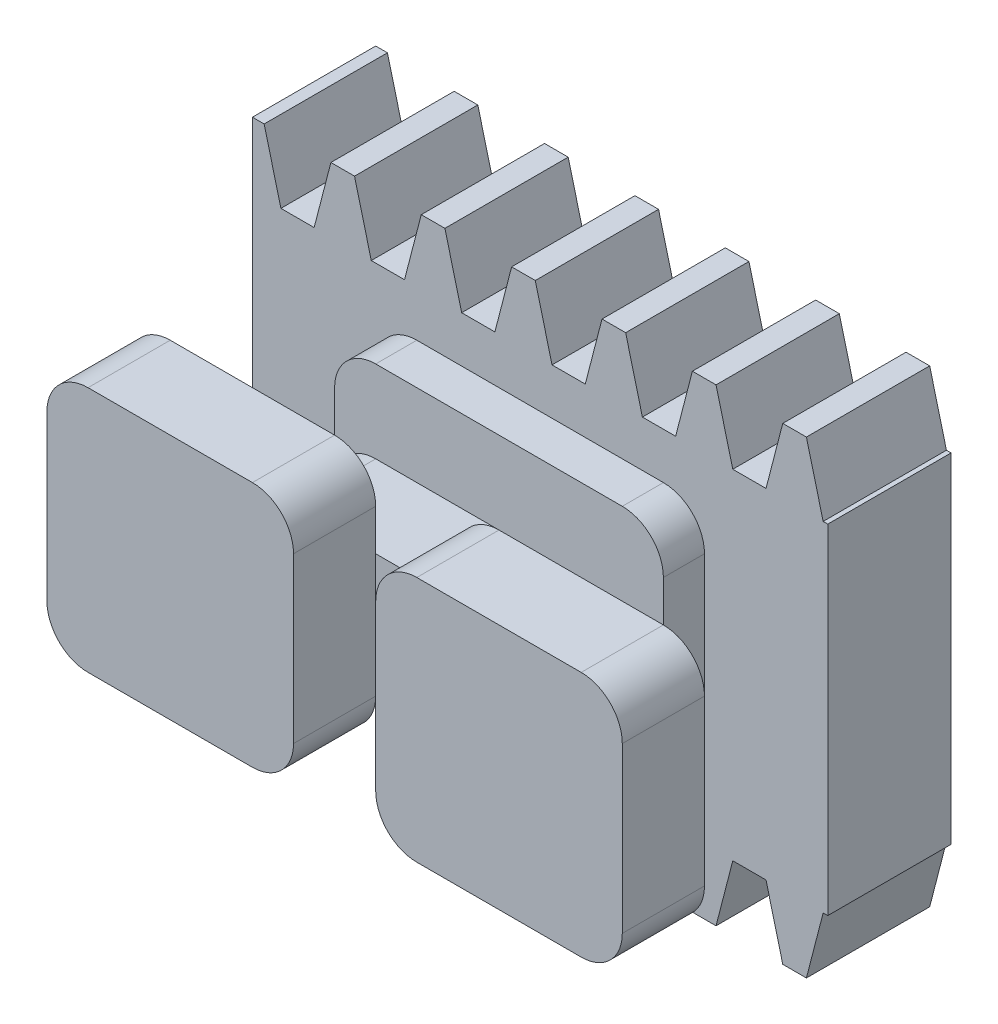
SolidWorks part; units mm, degrees
extrude "Blank" add sketch "BlankSke" against normal blind 3
sketch "BlankSke" plane through (0, 0, 0) normal (0, 0, 1) x (1, 0, 0)
  line L1 (0, 0) -> (25, 0)
  line L2 (0, 0) -> (0, 5.7)
  line L3 (0, 5.7) -> (25, 5.7)
  line L4 (25, 0) -> (25, 5.7)
  dimension "Length" = 25
ref_plane "Plane1" through (0, 0, 0) normal (0, 0, 1) x (1, 0, 0)
ref_plane "Plane2" through (0, 0, 0) normal (0, 1, 0) x (1, 0, 0)
ref_plane "Plane3" through (0, 0, 0) normal (1, 0, 0) x (0, 0, -1)
other "Configuration Table"
sketch "HoldingSke" plane through (0, 0, 0) normal (0, 1, 0) x (1, 0, 0)
  line L0 (0, 0) -> (0.1988, 1.4147)
  line L1 (-15, 0) -> (100, 0) construction
  line L2 (0, 0) -> (-2.1039, 2.3779)
  line L3 (0, 0) -> (-11.863, 4.5341)
  line L4 (0, 0) -> (8.4147, 1.9427)
  line L5 (0, 0) -> (-23.7986, -8.8762)
  line L6 (0, 0) -> (-10.5278, -7.1032)
  line L9 (-67.7845, 28.3722) -> (-43.5808, 34.6317)
  line L10 (-76.2, 3.0779) -> (-71.2, 3.0779)
  line L11 (0, 0) -> (-3, 0)
  line L12 (-76.2, 101.6) -> (-76.173, 101.6)
  line L13 (24.9733, 27.94) -> (52.9518, 28.4284)
  line L14 (24.9733, 27.94) -> (24.9743, 27.94)
  line L15 (24.9733, 27.94) -> (100.4006, 29.5858)
  circle A0 centre (0, 0) radius 19.05
  circle A1 centre (0, 0) radius 2.5
  circle A2 centre (0, 0) radius 12.7
  dimension "Num_teeth" = 13
  dimension "Width" = 3
  dimension "Length" = 25
  dimension "Pitch_height" = 5
sketch "TooCutSkeIll" plane through (0, 0, 0) normal (0, 0, 1) x (1, 0, 0)
  line L0 (-0.8064, 5.679) -> (-0.4386, 4.2569)
  line L1 (-0.2682, 4.125) -> (0.2682, 4.125)
  line L2 (0.4386, 4.2569) -> (0.8064, 5.679)
  line L3 (25, 5.7) -> (0, 5.7) construction
  line L4 (0, 0) -> (0, 64.897) construction
  line L5 (-13.208, 5) -> (12.954, 5) construction
  line L6 (0, 0) -> (25, 0) construction
  line L7 (0.6308, 5) -> (0.6308, 48.7463) construction
  line L8 (-0.6308, 5) -> (-0.6308, 48.7463) construction
  line L9 (0.8335, 5.7) -> (0.8335, 5.7254)
  line L10 (-0.8335, 5.7) -> (-0.8335, 5.7254)
  line L11 (-0.8335, 5.7254) -> (0.8335, 5.7254)
  arc A0 (0.2682, 4.125) -> (0.4386, 4.2569) centre (0.2682, 4.301) ccw
  arc A1 (-0.4386, 4.2569) -> (-0.2682, 4.125) centre (-0.2682, 4.301) ccw
  arc A2 (0.8335, 5.7) -> (0.8064, 5.679) centre (0.8335, 5.672) ccw
  arc A3 (-0.8064, 5.679) -> (-0.8335, 5.7) centre (-0.8335, 5.672) ccw
  dimension "Addendum_plus" = 0.7254
  dimension "Pitch_height" = 5
  dimension "Pressure_angle" = 14.5
  dimension "Gap_width" = 1.2616
  dimension "Dedendum" = 0.875
extrude "ToothCutIll" [suppressed] cut sketch "TooCutSkeIll" against normal through all
sketch "TooCutSkeSim" plane through (0, 0, 0) normal (0, 0, 1) x (1, 0, 0)
  line L0 (0.4045, 4.125) -> (-0.4045, 4.125)
  line L1 (0.8184, 5.7254) -> (0.4045, 4.125)
  line L2 (0, 17.4625) -> (0, 53.467) construction
  line L3 (0.8184, 5.7254) -> (-0.8184, 5.7254)
  line L6 (-0.8184, 5.7254) -> (-0.4045, 4.125)
  line L9 (-0.6308, 5) -> (0.6308, 5) construction
  line L10 (0, 0) -> (25, 0) construction
  line L11 (0.6308, 5) -> (0.6308, 53.467) construction
  line L12 (-0.6308, 5) -> (-0.6308, 53.467) construction
  dimension "Addendum_plus" = 0.7254
  dimension "Pitch_height" = 5
  dimension "Pressure_angle" = 14.5
  dimension "Gap_width" = 1.2616
  dimension "Dedendum" = 0.875
extrude "ToothCutSim" cut sketch "TooCutSkeSim" against normal through all
pattern_linear "TeethCuts" count 13 spacing 2.1991 along (1, 0, 0) of "ToothCutIll", "ToothCutSim"
mirror "镜向1" [suppressed]
mirror "镜向2" about plane through (0, 0, -3) normal (0, -1, 0) of "Blank", "ToothCutSim", "TeethCuts"
sketch "草图1" plane through (0, 0, 0) normal (-1, 0, 0) x (0, 0, 1)
  line L1 (0, 4.125) -> (0, -4.125) construction
  line L4 (-3, 0) -> (0, 0) construction
  line L5 (-3, 4.125) -> (-3, -4.125) construction
  line L7 (0, -3) -> (0, 3)
  line L8 (0, 3) -> (-2, 3.5)
  line L9 (-2, 3.5) -> (-2, -3.5)
  line L10 (0, -3) -> (-2, -3.5)
  point P11 (-2.5, 0)
  point P12 (-2, 0)
  dimension "D1" = 3
  dimension "D2" = 3.5
  dimension "D3" = 2
sketch "草图2" plane through (0, 0, -3) normal (0, 0, -1) x (-1, 0, 0)
  line L0 (0, 0) -> (-25, 0) construction
  line L1 (0, 4.125) -> (0, -4.125) construction
  line L2 (-25, -5.692) -> (-25, 5.692) construction
  circle A0 centre (-12.5, 0) radius 1.5
  dimension "D1" = 3
extrude "凸台-拉伸1" add sketch "草图2" along normal blind 2.5
sketch "草图3" plane through (0, 0, -5.5) normal (0, 0, -1) x (-1, 0, 0)
  circle A0 centre (-12.5, 0) radius 0.5
  dimension "D1" = 1
extrude "切除-拉伸3" cut sketch "草图3" against normal through all
sketch "草图4" plane through (0, 0, -3) normal (0, 0, -1) x (-1, 0, 0)
  line L0 (-12.5, 0) -> (-21.8848, 0) construction
  line L1 (-12.5, 0) -> (-2.5, 0) construction
  line L2 (-21.8848, 2.1496) -> (-21.8848, -2.1496)
  line L3 (-22.3956, 4.125) -> (-22.803, 5.7) construction
  line L4 (-2.5, 4.125) -> (-2.5, -4.125)
  line L6 (-1.7946, -4.125) -> (-2.6036, -4.125) construction
  line L7 (-22.3956, -4.125) -> (-22.803, -5.7) construction
  line L9 (-1.7946, 4.125) -> (-2.6036, 4.125) construction
  line L10 (-21.8848, 2.1496) -> (-21.8848, 5.9598)
  line L11 (-21.8848, 5.9598) -> (-25.6774, 5.9598)
  line L12 (-25.6774, 5.9598) -> (-25.6774, -6.5792)
  line L13 (-25.6774, -6.5792) -> (-21.8848, -6.5792)
  line L14 (-21.8848, -6.5792) -> (-21.8848, -2.1496)
  line L15 (-2.5, 4.125) -> (-2.5, 6.4022)
  line L16 (-2.5, 6.4022) -> (0, 6.4022)
  line L17 (0, 6.4022) -> (0, -6.0736)
  line L18 (0, -6.0736) -> (-2.5, -6.0736)
  line L19 (-2.5, -6.0736) -> (-2.5, -4.125)
  dimension "D2" = 10
extrude "切除-拉伸4" cut sketch "草图4" against normal blind 10
sketch "草图5" plane through (0, 0, 0) normal (0, 0, 1) x (1, 0, 0)
  line L0 (2.5, 2) -> (21.8848, 2)
  line L1 (2.5, 4.125) -> (2.5, -4.125) construction
  line L2 (21.8848, -4.125) -> (21.8848, 4.125) construction
  line L3 (21.8848, 2) -> (21.8848, -2)
  line L4 (21.8848, -2) -> (2.5, -2)
  line L5 (2.5, -2) -> (2.5, 2)
  point P8 (2.5, 0)
  point P9 (21.8848, 0)
  dimension "D1" = 4
sketch "草图6" plane through (0, 0, 0) normal (0, 0, 1) x (1, 0, 0)
  line L0 (1.1742, 0) -> (24.2349, 0) construction
  line L1 (8.5, 1) -> (8.5, -1)
  line L2 (8.5, -1) -> (16.5, -1)
  line L3 (16.5, -1) -> (16.5, 1)
  line L4 (16.5, 1) -> (8.5, 1)
  point P2 (16.5, 0)
  point P4 (12.5, 0)
  point P5 (8.5, 0)
  dimension "D1" = 2
  dimension "D2" = 8
  dimension "D3" = 4
extrude "凸台-拉伸3" add sketch "草图6" along normal blind 3
sketch "草图7" plane through (0, 0, 3) normal (0, 0, 1) x (1, 0, 0)
  line L0 (5.5, 3) -> (11.5, 3)
  line L1 (19.5, 3) -> (19.5, -3)
  line L2 (19.5, -3) -> (13.5, -3)
  line L3 (5.5, -3) -> (5.5, 3)
  line L5 (16.5, 1) -> (8.5, 1) construction
  line L6 (8.5, -1) -> (16.5, -1) construction
  line L7 (8.5, 1) -> (8.5, -1) construction
  line L8 (16.5, -1) -> (16.5, 1) construction
  line L9 (11.5, 3) -> (11.5, -3)
  line L10 (13.5, 3) -> (13.5, -3)
  line L11 (13.5, 3) -> (19.5, 3)
  line L12 (11.5, -3) -> (5.5, -3)
  dimension "D1" = 2
  dimension "D2" = 2
  dimension "D3" = 3
  dimension "D4" = 3
  dimension "D5" = 6
  dimension "D6" = 6
extrude "凸台-拉伸4" add sketch "草图7" along normal blind 2
fillet "圆角1" radius 1 4 edges at (16.5, -1, 1.5) (8.5, -1, 1.5) (16.5, 1, 1.5) (8.5, 1, 1.5)
fillet "圆角2" radius 1 8 edges at (5.5, -3, 4) (5.5, 3, 4) (11.5, 3, 4) (11.5, -3, 4) (13.5, -3, 4) (13.5, 3, 4) (19.5, 3, 4) (19.5, -3, 4)
sketch "草图8" plane through (0, 0, 0) normal (0, 0, 1) x (1, 0, 0)
  line L15 (8.5, 3) -> (8.5, -3)
  line L16 (10.5, 3) -> (6.5, 3) construction
  line L17 (6.5, -3) -> (10.5, -3) construction
  line L18 (8.5, -3) -> (16.5, -3)
  line L19 (14.5, -3) -> (18.5, -3) construction
  line L20 (16.5, -3) -> (16.5, 3)
  line L21 (16.5, 3) -> (8.5, 3)
  line L22 (11.5, -2) -> (11.5, 2) construction
  dimension "D1" = 3
  dimension "D2" = 8
extrude "凸台-拉伸5" add sketch "草图8" along normal blind 1
fillet "圆角5" radius 1 4 edges at (16.5, -3, 0.5) (8.5, -3, 0.5) (8.5, 3, 0.5) (16.5, 3, 0.5)
sketch "草图9" plane through (0, 0, 0) normal (0, 0, 1) x (1, 0, 0)
  line L0 (5.5, 0) -> (5.5, -6.2232)
  line L1 (5.5, 2) -> (5.5, -2) construction
  line L2 (5.5, -6.2232) -> (2.2382, -6.2232)
  line L3 (2.2382, -6.2232) -> (2.2382, 6.2496)
  line L4 (2.2382, 6.2496) -> (5.5, 6.2496)
  line L5 (5.5, 6.2496) -> (5.5, 0)
  line L6 (19.5, 0) -> (19.5, -6.2232)
  line L7 (19.5, -2) -> (19.5, 2) construction
  line L8 (19.5, -6.2232) -> (22.4063, -6.2232)
  line L9 (22.4063, -6.2232) -> (22.4063, 6.2496)
  line L10 (22.4063, 6.2496) -> (19.5, 6.2496)
  line L11 (19.5, 6.2496) -> (19.5, 0)
extrude "切除-拉伸5" cut sketch "草图9" against normal through all
equation "' \"Module@HoldingSke\" = 6.35"
equation "' \"Num_teeth@HoldingSke\" = 12"
equation "' \"Ap@HoldingSke\" =  20"
equation "' \"Ap@HoldingSke\" = 20"
equation "' \"Width@HoldingSke\" = 0.25 * 25.4"
equation "' \"Show_teeth@HoldingSke\" = 500"
equation "' \"Backlash@HoldingSke\" = 0.009 * 25.4"
equation "' \"Addendum_fac@HoldingSke\" = 1.0"
equation "' \"Dedendum_fac@HoldingSke\" = 1.25"
equation "' \"Dedendum_add@HoldingSke\" = 0.00005 * 25.4"
equation "' \"Clearance_fac@HoldingSke\" = 0.25"
equation "' \"Pitch_height@HoldingSke\" = 1 * 25.4"
equation "' \"Length@HoldingSke\" = 4.71 * 25.4"
equation "\"Pitch@HoldingSke\" = 1 / \"Module@HoldingSke\""
equation "\"MPH@HoldingSke\" = \"Dedendum_fac@HoldingSke\" / \"Pitch@HoldingSke\" + 2 * \"Dedendum_add@HoldingSke\" + 0.002 * 25.4"
equation "\"MPH@HoldingSke\" = ((sgn( \"MPH@HoldingSke\" - \"Pitch_height@HoldingSke\")+1)*( \"MPH@HoldingSke\" - \"Pitch_height@HoldingSke\"))/2 + \"Pitch_height@HoldingSke\""
equation "\"Blank_height@BlankSke\" = \"Pitch_height@HoldingSke\" + \"Addendum_fac@HoldingSke\"  / \"Pitch@HoldingSke\" "
equation "\"Length@BlankSke\" =  \"Length@HoldingSke\""
equation "\"Face_width@Blank\" = \"Width@HoldingSke\""
equation "\"Pressure_angle@TooCutSkeIll\" = \"Ap@HoldingSke\""
equation "\"Addendum_plus@TooCutSkeIll\" =  \"Addendum_fac@HoldingSke\"  / \"Pitch@HoldingSke\" + 0.001 *25.4"
equation "\"Dedendum@TooCutSkeIll\" = \"Dedendum_fac@HoldingSke\"  / \"Pitch@HoldingSke\""
equation "\"Pitch_height@TooCutSkeIll\" =  \"MPH@HoldingSke\""
equation "\"Gap_width@TooCutSkeIll\" = 3.14159265 / 2 / \"Pitch@HoldingSke\" + 6 * \"Backlash@HoldingSke\""
equation "\"Pressure_angle@TooCutSkeSim\" = \"Ap@HoldingSke\""
equation "\"Addendum_plus@TooCutSkeSim\" =  \"Addendum_fac@HoldingSke\"  / \"Pitch@HoldingSke\" + 0.001 * 25.4"
equation "\"Dedendum@TooCutSkeSim\" = \"Dedendum_fac@HoldingSke\"  / \"Pitch@HoldingSke\""
equation "\"Pitch_height@TooCutSkeSim\" =  \"MPH@HoldingSke\""
equation "\"Gap_width@TooCutSkeSim\" = 3.14159265 / 2 / \"Pitch@HoldingSke\" + 6 * \"Backlash@HoldingSke\""
equation "\"Root_fillet@TooCutSkeIll\" = \"Clearance_fac@HoldingSke\" / \"Pitch@HoldingSke\" + \"Dedendum_add@HoldingSke\""
equation "\"Break_rad@TooCutSkeIll\" = 0.02 / \"Pitch@HoldingSke\" * 2"
equation "\"Linear_pitch@TeethCuts\" = 3.14159265 / \"Pitch@HoldingSke\""
equation "\"Num_teeth@HoldingSke\" = int( ( \"Length@HoldingSke\" + 0 ) / (3.14159265 / \"Pitch@HoldingSke\")) + 0.9999  + 1"
equation " \"Num_teeth@TeethCuts\" = int( \"Show_teeth@HoldingSke\" ) + 1"
equation " \"Num_teeth@TeethCuts\" = ((sgn( \"Num_teeth@TeethCuts\" - \"Num_teeth@HoldingSke\" )-1)*( \"Num_teeth@TeethCuts\" - \"Num_teeth@HoldingSke\" ))/-2+ \"Num_teeth@HoldingSke\""
equation " \"Num_teeth@TeethCuts\" = ((sgn( \"Num_teeth@TeethCuts\" - 2.0)+1)*( \"Num_teeth@TeethCuts\" - 2.0))/2 +2.0"
